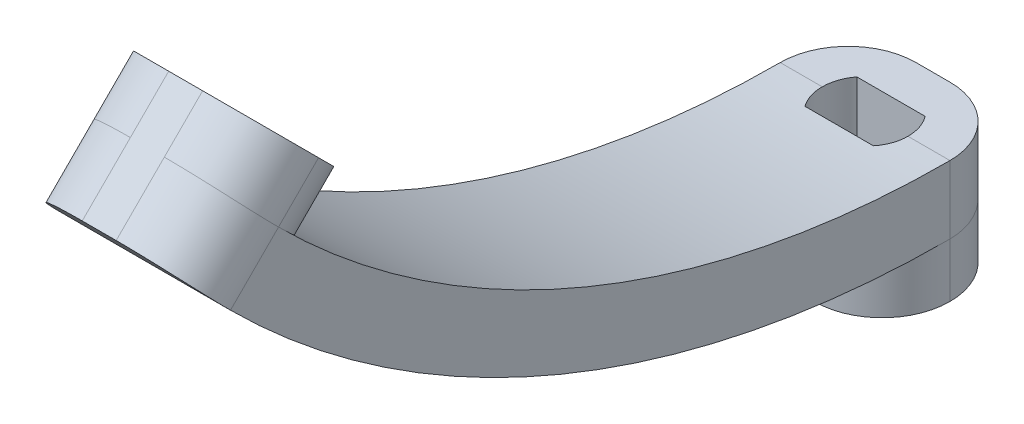
SolidWorks part; units mm, degrees
ref_plane "Front Plane" through (0, 0, 0) normal (0, 0, 1) x (1, 0, 0)
ref_plane "Top Plane" through (0, 0, 0) normal (0, 1, 0) x (1, 0, 0)
ref_plane "Right Plane" through (0, 0, 0) normal (1, 0, 0) x (0, 0, -1)
sketch "Sketch1" plane through (0, 0, 0) normal (1, 0, 0) x (0, 0, -1)
  line L0 (-6.3631, 62.521) -> (-39.9507, 28.9334) construction
  line L1 (-42.2788, 26.6053) -> (-39.9507, 28.9334) construction
  line L2 (0, 3.2924) -> (0, 0) construction
  line L3 (0, 7.2924) -> (0, 3.2924)
  line L5 (-42.2788, 26.6053) -> (-45.114, 23.7701)
  arc A0 (0, 3.2924) -> (-45.114, 23.7701) centre (0.0009, 63.2281) cw
  arc A1 (0, 7.2924) -> (-42.2788, 26.6053) centre (0.0009, 63.2281) cw
  dimension "D2" = 4
extrude "Boss-Extrude1" add sketch "Sketch1" along normal mid plane 10
sketch "Sketch2" plane through (0, -5.5086, 5.5086) normal (0, -0.7071, 0.7071) x (1, 0, 0)
  line L0 (5, 48.7084) -> (-5, 48.7084) construction
  line L1 (0, 48.7084) -> (0, 40.7084) construction
  line L2 (0, 44.7084) -> (-5, 44.7084) construction
  line L3 (-5, 48.7084) -> (-5, 5.1565) construction
  line L4 (0, 44.7084) -> (5, 44.7084) construction
  line L5 (5, 5.1565) -> (5, 48.7084) construction
  circle A0 centre (0, 44.7084) radius 4
  dimension "D1" = 8
extrude "Boss-Extrude2" add sketch "Sketch2" along normal up to next
fillet "Fillet1" radius 4 2 edges at (-5, 25.1877, 43.6964) (5, 25.1877, 43.6964)
sketch "Sketch5" plane through (0, -5.5086, 5.5086) normal (0, 0.7071, -0.7071) x (1, 0, 0)
  circle A0 centre (0, -44.7084) radius 1.75
  dimension "D1" = 3.5
sketch "Sketch8" plane through (0, 0, 0) normal (0, 0, -1) x (-1, 0, 0)
  line L1 (-5, 7.2924) -> (5, 7.2924)
  line L2 (-5, 7.2924) -> (-5, 3.2924)
  line L3 (-5, 3.2924) -> (5, 3.2924)
  line L4 (5, 7.2924) -> (5, 3.2924)
extrude "Boss-Extrude3" add sketch "Sketch8" along normal blind 4
sketch "Sketch9" plane through (0, 0, 0) normal (0, 1, 0) x (1, 0, 0)
  circle A0 centre (0, 0) radius 4
  dimension "D1" = 8
extrude "Boss-Extrude4" add sketch "Sketch9" along normal up to next
fillet "Fillet2" radius 4 2 edges at (5, 5.2924, -4) (-5, 5.2924, -4)
sketch "Sketch12" plane through (0, -5.5086, 5.5086) normal (0, 0.7071, -0.7071) x (1, 0, 0)
  line L0 (5, -44.7084) -> (5, -5.1565) construction
  line L1 (-5, -40.7084) -> (5, -40.7084)
  line L2 (-5, -40.7084) -> (-5, -48.7084)
  line L3 (-5, -48.7084) -> (5, -48.7084)
  line L4 (5, -40.7084) -> (5, -48.7084)
  line L5 (-5, -40.7084) -> (5, -48.7084) construction
  line L6 (-5, -48.7084) -> (5, -40.7084) construction
  point P0 (0, -44.7084)
  point P6 (0, -48.7084)
extrude "Boss-Extrude5" add sketch "Sketch12" against normal up to surface (3.2924 mm away) up to face at (0.0347, 19.5061, 30.8808)
fillet "Fillet3" radius 4 4 edges at (-5, 22.1125, 35.4579) (-5, 27.7693, 41.1147) (5, 27.7693, 41.1147) (5, 22.1125, 35.4579)
extrude "Cut-Extrude4" cut sketch "Sketch5" against normal blind 6.59
sketch "Sketch14" plane through (0, -5.5086, 5.5086) normal (0, 0.7071, -0.7071) x (1, 0, 0)
  circle A0 centre (0, -44.7084) radius 5.9982
extrude "Cut-Extrude6" cut sketch "Sketch14" against normal blind 0.1
sketch "Sketch15" plane through (0, 0, 0) normal (0, -1, 0) x (1, 0, 0)
  line L0 (5, 0) -> (5, 42.38) construction
  line L1 (-5, -4) -> (5, -4)
  line L2 (-5, -4) -> (-5, 4)
  line L3 (-5, 4) -> (5, 4)
  line L4 (5, -4) -> (5, 4)
  line L5 (-5, -4) -> (5, 4) construction
  line L6 (-5, 4) -> (5, -4) construction
  point P0 (0, 0)
  point P8 (0, -4)
extrude "Boss-Extrude6" add sketch "Sketch15" against normal up to surface (3.426 mm away) up to face at (0.1362, 11.9066, 22.95)
fillet "Fillet4" radius 4 4 edges at (5, 1.7131, 4) (5, 1.713, -4) (-5, 1.7131, 4) (-5, 1.713, -4)
sketch "Sketch13" plane through (0, 0, 0) normal (0, -1, 0) x (1, 0, 0)
  circle A0 centre (0, 0) radius 9.9521
extrude "Cut-Extrude5" cut sketch "Sketch13" against normal blind 0.1
sketch "Sketch10" plane through (0, 0, 0) normal (0, 1, 0) x (1, 0, 0)
  line L0 (-2.0125, 1.525) -> (2.0125, 1.525)
  line L1 (-2.0125, -1.525) -> (2.0125, -1.525)
  line L2 (0, 1.525) -> (0, 0) construction
  line L3 (0, 0) -> (0, -1.525) construction
  arc A0 (-2.0125, 1.525) -> (-2.0125, -1.525) centre (0, 0) ccw
  arc A1 (2.0125, -1.525) -> (2.0125, 1.525) centre (0, 0) ccw
  dimension "D1" = 5.05
  dimension "D2" = 3.05
extrude "Cut-Extrude2" cut sketch "Sketch10" along normal through all
